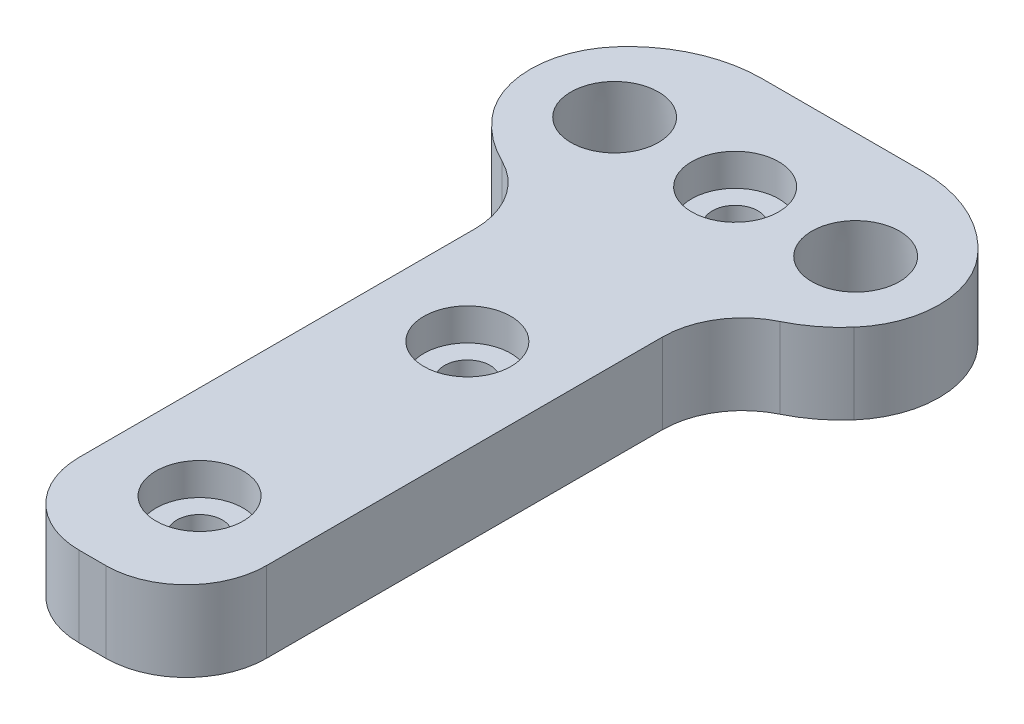
SolidWorks part; units mm, degrees
ref_plane "Front" through (0, 0, 0) normal (0, 0, 1) x (1, 0, 0)
ref_plane "Top" through (0, 0, 0) normal (0, 1, 0) x (1, 0, 0)
ref_plane "Right" through (0, 0, 0) normal (1, 0, 0) x (0, 0, -1)
sketch "Sketch1" plane through (0, 0, 0) normal (0, 1, 0) x (1, 0, 0)
  line L0 (3.5, 6) -> (8, 6)
  line L2 (-3.5, 6) -> (-3.5, -14)
  line L3 (-3.5, -14) -> (3.5, -14)
  line L4 (3.5, 6) -> (3.5, -14)
  line L5 (-8, 14) -> (8, 14)
  line L6 (-8, 14) -> (-8, 6)
  line L7 (-8, 6) -> (-3.5, 6)
  line L8 (8, 14) -> (8, 6)
  line L9 (0, 14) -> (0, -14) construction
  line L10 (-3.5, 6) -> (3.5, 6) construction
  point P10 (0, 0)
  point P12 (0, -14)
  point P13 (0, 6)
  dimension "D1" = 8
  dimension "D2" = 20
  dimension "D3" = 16
  dimension "D4" = 7
extrude "Boss-Extrude1" add sketch "Sketch1" along normal blind 3
sketch "Sketch2" plane through (0, 0, 0) normal (0, 1, 0) x (1, 0, 0)
  line L0 (0, 14) -> (0, -14) construction
  line L1 (8, 14) -> (-8, 14) construction
  line L2 (-3.5, -14) -> (3.5, -14) construction
  line L3 (-8, 10) -> (8, 10) construction
  line L4 (-8, 14) -> (-8, 6) construction
  line L5 (8, 6) -> (8, 14) construction
  circle A0 centre (0, 10) radius 0.5
  circle A1 centre (0, 0) radius 0.5
  circle A2 centre (0, -10) radius 0.5
  circle A3 centre (-4.5, 10) radius 0.5
  circle A4 centre (4.5, 10) radius 0.5
  dimension "D1" = 3.5
  dimension "D3" = 1
  dimension "D2" = 3.5
  dimension "D4" = 10
  dimension "D5" = 4
hole_wizard "CBORE for M5 Hex Head Bolt1" positions "Sketch3" profile "Sketch4" counterbore size "M5" standard "ISO"
sketch "Sketch3" plane through (0, 3, 0) normal (0, 1, 0) x (1, 0, 0)
  point P0 (0, 10)
  point P3 (0, 0)
  point P6 (0, -10)
sketch "Sketch4" plane through (0, 3, -10) normal (1, 0, 0) x (0, 0, 1)
  line L0 (0, 0) -> (0, 3)
  line L1 (0, 3) -> (0.85, 3)
  line L2 (0.85, 3) -> (0.85, 1.2)
  line L3 (0.85, 1.2) -> (1.625, 1.2)
  line L4 (1.625, 1.2) -> (1.625, 0)
  line L5 (1.625, 0) -> (0, 0)
  line L10 (0, 3) -> (-0.85, 3) construction
  line L11 (0, -6.35) -> (0, 107.95) construction
  dimension "Hole Dia." = 1.7
  dimension "Hole Depth" = 3
  dimension "C'Bore Dia." = 3.25
  dimension "C'Bore Depth" = 1.2
  dimension "Drill Angle" = 180
fillet "Fillet1" radius 5 4 edges at (-8, 1.5, -6) (-8, 1.5, -14) (8, 1.5, -6) (8, 1.5, -14)
fillet "Fillet2" radius 3.5 2 edges at (7.9015, 1.5, -9.9875) (-7.9015, 1.5, -9.9875)
fillet "Fillet3" radius 3 4 edges at (-3.5, 1.5, -6) (3.5, 1.5, -6) (-3.5, 1.5, 14) (3.5, 1.5, 14)
hole_wizard "CSK for M2 Countersunk Flat Head Screw2" positions "Sketch7" profile "Sketch8" countersink size "M2" standard "ISO" end condition through all
sketch "Sketch7" plane through (0, 0, 0) normal (0, -1, 0) x (-1, 0, 0)
  point P0 (4.5, 10)
  point P3 (-4.5, 10)
sketch "Sketch8" plane through (-4.5, 0, -10) normal (1, 0, 0) x (0, 0, -1)
  line L0 (0, 0) -> (0, 3)
  line L1 (0, 3) -> (1.6, 3)
  line L2 (1.6, 3) -> (1.6, 3.3753)
  line L3 (1.6, 3.3753) -> (1.925, 0)
  line L5 (1.925, 0) -> (0, 0)
  line L6 (-1.6, 3.3753) -> (-1.925, 0) construction
  line L11 (0, -6.35) -> (0, 107.95) construction
  dimension "Thru Hole Dia." = 3.2
  dimension "Thru Hole Depth" = 3
  dimension "Near C'Sink Dia." = 3.85
  dimension "Near C'Sink Angle" = 11
